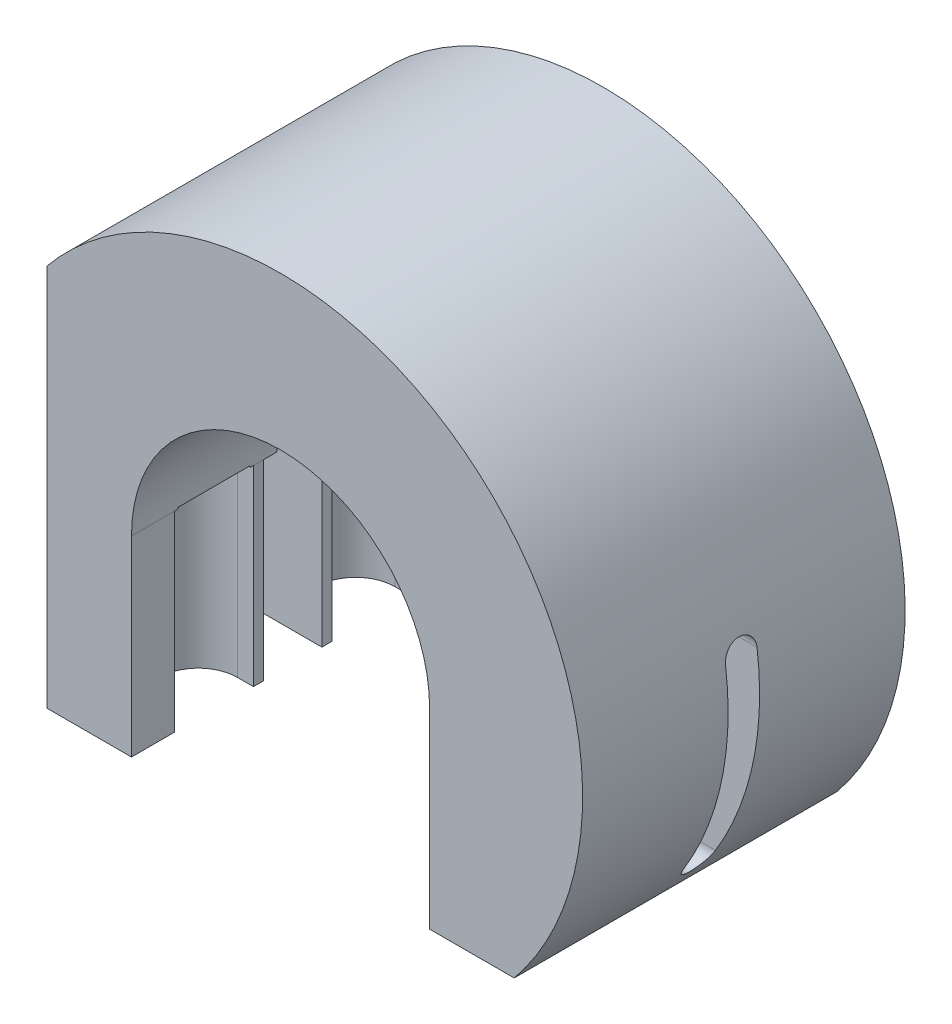
SolidWorks part; units mm, degrees
ref_plane "Front Plane" through (0, 0, 0) normal (0, 0, 1) x (1, 0, 0)
ref_plane "Top Plane" through (0, 0, 0) normal (0, 1, 0) x (1, 0, 0)
ref_plane "Right Plane" through (0, 0, 0) normal (1, 0, 0) x (0, 0, -1)
sketch "Sketch1" plane through (0, 0, 0) normal (0, 0, 1) x (1, 0, 0)
  line L0 (-29.7, 24.3407) -> (-29.7, -24.3407)
  line L1 (-29.7, -24.3407) -> (29.7, -24.3407)
  circle A0 centre (0, 0) radius 38.4
  dimension "D1" = 76.8
  dimension "D2" = 29.7
extrude "Boss-Extrude1" add sketch "Sketch1" along normal blind 41 contours L0 A0 region at (2.5555, 4.6425, 0)
sketch "Sketch2" plane through (0, 0, 41) normal (0, 0, 1) x (1, 0, 0)
  line L0 (18.95, 0) -> (18.95, -33.3985)
  line L1 (-18.95, 0) -> (-18.95, -33.3985)
  line L3 (-29.7, 24.3407) -> (-29.7, -24.3407)
  line L6 (-29.7, -24.3407) -> (29.7, -24.3407)
  line L7 (-29.7, -24.3407) -> (29.7, -24.3407)
  circle A0 centre (0, 0) radius 18.95
  arc A1 (29.7, -24.3407) -> (-29.7, 24.3407) centre (0, 0) ccw construction
  arc A3 (29.7, -24.3407) -> (-29.7, 24.3407) centre (0, 0) ccw
  arc A4 (-18.95, -33.3985) -> (18.95, -33.3985) centre (0, 0) ccw
  arc M5 (29.7, -24.3407) -> (-29.7, 24.3407) centre (0, 0) ccw
  dimension "D1" = 37.9
  dimension "D2" = 0
extrude "Cut-Extrude1" cut sketch "Sketch2" against normal blind 41 contours A0 | A0 L1 L0 M5 region at (0, 0, 41) region at (18.4996, -12.1704, 41)
ref_plane "Plane2" through (0, 0, 0) normal (0, 1, 0) x (1, 0, 0)
ref_plane "Plane3" through (0, 0.2, 0) normal (0, 1, 0) x (1, 0, 0)
sketch "Sketch4" plane through (0, -24.3407, 0) normal (0, -1, 0) x (-1, 0, 0)
  line L0 (18.95, 0) -> (18.95, -41) construction
  line L1 (18.95, -20.5) -> (-18.95, -20.5) construction
  line L2 (18.95, 0) -> (18.95, -41) construction
  line L3 (-18.95, 0) -> (-18.95, -41) construction
  line L4 (20.95, -5.5) -> (18.95, -5.5)
  line L5 (18.95, -5.5) -> (18.95, -15.5)
  line L6 (18.95, -15.5) -> (20.95, -15.5)
  line L7 (18.95, -25.5) -> (20.95, -25.5)
  line L8 (18.95, -35.5) -> (18.95, -25.5)
  line L9 (20.95, -35.5) -> (18.95, -35.5)
  line L10 (0, 0) -> (0, -41) construction
  line L11 (-18.95, -41) -> (18.95, -41) construction
  line L12 (-20.95, -35.5) -> (-18.95, -35.5)
  line L13 (-18.95, -35.5) -> (-18.95, -25.5)
  line L14 (-18.95, -25.5) -> (-20.95, -25.5)
  line L15 (-18.95, -15.5) -> (-20.95, -15.5)
  line L16 (-18.95, -5.5) -> (-18.95, -15.5)
  line L17 (-20.95, -5.5) -> (-18.95, -5.5)
  line L18 (18.95, 0) -> (18.95, -41) construction
  line L19 (18.95, -16.8) -> (26.35, -16.8)
  line L20 (18.95, -16.8) -> (18.95, -24.2)
  line L21 (18.95, -24.2) -> (26.35, -24.2)
  line L22 (26.35, -16.8) -> (26.35, -24.2)
  line L23 (-18.95, -24.2) -> (-26.35, -24.2)
  line L24 (-26.35, -16.8) -> (-26.35, -24.2)
  line L25 (-18.95, -16.8) -> (-26.35, -16.8)
  line L26 (-18.95, -16.8) -> (-18.95, -24.2)
  circle A0 centre (20.95, -10.5) radius 5
  circle A2 centre (20.95, -30.5) radius 5
  circle A3 centre (-20.95, -30.5) radius 5
  circle A4 centre (-20.95, -10.5) radius 5
  point P43 (18.95, -20.5)
  line M24 (18.95, 0) -> (18.95, -41)
  dimension "D1" = 10
  dimension "D3" = 10
  dimension "D2" = 2
  dimension "D4" = 7.4
extrude "Cut-Extrude2" cut sketch "Sketch4" against normal up to surface (24.5407 mm away) contours A2 L8 | A2 L8 | L9 A2 L8 | L8 A2 L7 | A0 L5 | A0 L5 L6 | A0 L4 L5 | A3 L13 | A3 L12 L13 | L13 A3 | A4 L16 | L16 A4 L15 | L17 A4 L16 | L26 L25 L24 L23 | L22 L19 L21 M24 region at (-19.4457, -24.3407, 5.6243) region at (-19.4457, -24.3407, 25.6243) region at (-22.65, -24.3407, 20.5) region at (-22.0425, -24.3407, 10.5) region at (-19.4457, -24.3407, 15.3757) region at (-22.0425, -24.3407, 30.5) region at (-17.7125, -24.3407, 30.5) region at (-19.4457, -24.3407, 35.3757) region at (19.4457, -24.3407, 35.3757) region at (22.0425, -24.3407, 30.5) region at (17.7125, -24.3407, 30.5) region at (19.4457, -24.3407, 15.3757) region at (22.0425, -24.3407, 10.5) region at (19.4457, -24.3407, 5.6243) region at (22.65, -24.3407, 20.5) up to plane "Plane3"
sketch "Sketch6" plane through (0, 0, 0) normal (1, 0, 0) x (0, 0, -1)
  line L0 (-20.5, 5) -> (-20.5, -20) construction
  line L1 (-18.5, 5) -> (-18.5, -20)
  line L2 (-22.5, 5) -> (-22.5, -20)
  line L3 (-41, -24.3407) -> (0, -24.3407) construction
  arc A0 (-18.5, 5) -> (-22.5, 5) centre (-20.5, 5) ccw
  arc A1 (-22.5, -20) -> (-18.5, -20) centre (-20.5, -20) ccw
  point P2 (-20.5, -7.5)
  point P7 (0, 0)
  point P11 (-20.5, -24.3407)
  point P12 (-20.5, 8.0069)
  dimension "D2" = 2
  dimension "D1" = 25
  dimension "D3" = 5
extrude "Cut-Extrude4" cut sketch "Sketch6" against normal through all both and the other way through all
